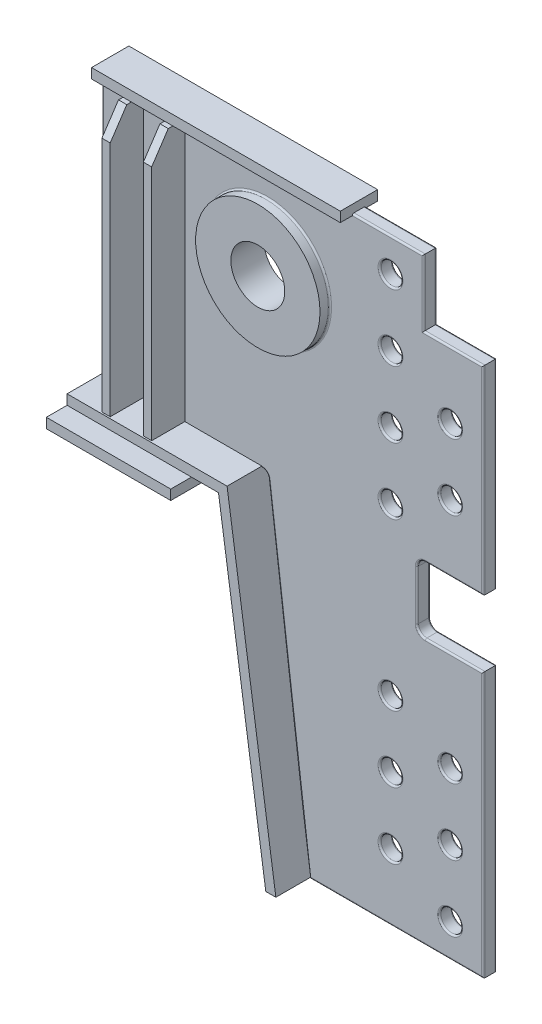
SolidWorks part; units mm, degrees
ref_plane "前视" through (0, 0, 0) normal (0, 0, 1) x (1, 0, 0)
ref_plane "上视" through (0, 0, 0) normal (0, 1, 0) x (1, 0, 0)
ref_plane "右视" through (0, 0, 0) normal (1, 0, 0) x (0, 0, -1)
sketch "草图1" plane through (0, 0, 0) normal (0, 0, 1) x (1, 0, 0)
  line L0 (0, -320) -> (-70, -320)
  line L1 (-72, 0) -> (-460, 0)
  line L2 (-40, 116.6722) -> (-40, -759.2574) construction
  line L3 (0, -720) -> (-210, -720)
  line L4 (-460, 0) -> (-460, -320)
  line L5 (-80, -330) -> (-80, -390)
  line L6 (-70, -400) -> (0, -400)
  line L7 (0, -400) -> (0, -720)
  line L8 (-112, 271.0914) -> (-112, -671.0914) construction
  line L9 (-775.8996, -110) -> (-214.577, -110) construction
  line L15 (-210, -720) -> (-259.124, -327.0077)
  line L16 (-460, -320) -> (-267.0623, -320)
  line L17 (-72, 0) -> (-72, -80)
  line L18 (-72, -80) -> (0, -80)
  line L19 (0, -80) -> (0, -320)
  arc A0 (-80, -330) -> (-70, -320) centre (-70, -330) cw
  arc A1 (-70, -400) -> (-80, -390) centre (-70, -390) cw
  circle A2 centre (-112, -40) radius 13
  circle A3 centre (-112, -120) radius 13
  circle A4 centre (-112, -200) radius 13
  circle A5 centre (-112, -280) radius 13
  circle A6 centre (-40, -160) radius 13
  circle A7 centre (-40, -240) radius 13
  circle A8 centre (-40, -680) radius 13
  circle A9 centre (-40, -600) radius 13
  circle A10 centre (-40, -520) radius 13
  arc A11 (-259.124, -327.0077) -> (-267.0623, -320) centre (-267.0623, -328) ccw
  circle A12 centre (-112, -640) radius 13
  circle A13 centre (-112, -560) radius 13
  circle A14 centre (-112, -480) radius 13
  circle A15 centre (-260, -110) radius 37.5
  point P11 (-80, -320)
  point P49 (-260, -320)
  dimension "D4" = 10
  dimension "D5" = 10
  dimension "D13" = 72
  dimension "D14" = 80
  dimension "D18" = 72
  dimension "D20" = 80
  dimension "D24" = 8
  dimension "D25" = 40
  dimension "D26" = 40
  dimension "D32" = 26
  dimension "D34" = 75
  dimension "D3" = 80
  dimension "D6" = 720
  dimension "D7" = 72
  dimension "D8" = 320
  dimension "D9" = 320
  dimension "D10" = 460
  dimension "D11" = 80
  dimension "D12" = 40
  dimension "D15" = 40
  dimension "D16" = 80
  dimension "D17" = 80
  dimension "D19" = 80
  dimension "D21" = 210
  dimension "D22" = 392.9923
  dimension "D23" = 40
  dimension "D27" = 80
  dimension "D28" = 80
  dimension "D29" = 40
  dimension "D30" = 80
  dimension "D31" = 80
  dimension "D33" = 110
  dimension "D35" = 200
extrude "基体-拉伸" add sketch "草图1" along normal blind 16
sketch "草图2" plane through (0, 0, 16) normal (0, 0, 1) x (1, 0, 0)
  line L0 (-460, 0) -> (-460, -320) construction
  line L1 (-72, 0) -> (-460, 0) construction
  circle A0 centre (-260, -110) radius 32.5
  circle A1 centre (-260, -110) radius 75
  dimension "D1" = 65
  dimension "D4" = 150
  dimension "D2" = 200
  dimension "D3" = 110
extrude "凸台-拉伸1" add sketch "草图2" along normal blind 12 and the other way blind 28
fillet "圆角1" radius 2 28 edges at (-185, -110, 16) (-99, -560, 16) (-27, -600, 16) (-27, -240, 16) (-35, -320, 16) (-77.0711, -322.9289, 16) (-80, -360, 16) (-77.0711, -397.0711, 16) (-35, -400, 16) (0, -560, 16) (-105, -720, 16) (-234.562, -523.5039, 16) (-261.7678, -322.0026, 16) (-363.5311, -320, 16) (-460, -160, 16) (-266, 0, 16) (-27, -680, 16) (-27, -520, 16) (-99, -480, 16) (-99, -640, 16) (-99, -280, 16) (-99, -120, 16) (-72, -40, 16) (-36, -80, 16) (0, -200, 16) (-99, -40, 16) (-99, -200, 16) (-27, -160, 16)
fillet "圆角2" radius 2 28 edges at (-185, -110, 0) (-99, -560, 0) (-27, -600, 0) (-27, -240, 0) (-266, 0, 0) (-460, -160, 0) (-363.5311, -320, 0) (-261.7678, -322.0026, 0) (-234.562, -523.5039, 0) (-105, -720, 0) (0, -560, 0) (-35, -400, 0) (-77.0711, -397.0711, 0) (-80, -360, 0) (-77.0711, -322.9289, 0) (-35, -320, 0) (-27, -680, 0) (-27, -520, 0) (-99, -480, 0) (-99, -640, 0) (-99, -280, 0) (-99, -120, 0) (0, -200, 0) (-36, -80, 0) (-72, -40, 0) (-99, -40, 0) (-99, -200, 0) (-27, -160, 0)
sketch "草图3" plane through (0, 0, 16) normal (0, 0, 1) x (1, 0, 0)
  line L0 (-74, -2) -> (-458, -2) construction
  line L1 (-420, -2) -> (-410, -2)
  line L2 (-420, -2) -> (-420, -318)
  line L3 (-420, -318) -> (-410, -318)
  line L4 (-410, -2) -> (-410, -318)
  line L5 (-458, -318) -> (-267.0623, -318) construction
  line L6 (-460, -320) -> (-460, 0) construction
  line L7 (-370, -2) -> (-360, -2)
  line L8 (-370, -2) -> (-370, -318)
  line L9 (-370, -318) -> (-360, -318)
  line L10 (-360, -2) -> (-360, -318)
  dimension "D1" = 10
  dimension "D2" = 10
  dimension "D3" = 40
  dimension "D4" = 40
extrude "凸台-拉伸2" add sketch "草图3" along normal blind 40 and the other way blind 56
sketch "草图4" plane through (-420, 0, 0) normal (-1, 0, 0) x (0, 0, 1)
  line L0 (-20, -2) -> (-45.5, -32)
  line L1 (0, -2) -> (-40, -2) construction
  line L3 (-20, -2) -> (-45.5, -2)
  line L4 (-45.5, -2) -> (-45.5, -32)
  dimension "D1" = 30
  dimension "D2" = 25.5
extrude "切除-拉伸1" cut sketch "草图4" against normal through all
sketch "草图5" plane through (-420, 0, 0) normal (-1, 0, 0) x (0, 0, 1)
  line L0 (36, -2) -> (56, -32)
  line L1 (56, -2) -> (16, -2) construction
  line L2 (56, -2) -> (56, -318) construction
  line L3 (36, -2) -> (56, -2)
  line L4 (56, -2) -> (56, -32)
  dimension "D1" = 30
extrude "切除-拉伸2" cut sketch "草图5" against normal through all
sketch "草图6" plane through (0, 0, 16) normal (0, 0, 1) x (1, 0, 0)
  line L0 (-460, -320) -> (-460, 0) construction
  line L1 (-267.0623, -318) -> (-460, -318)
  line L2 (-267.0623, -318) -> (-208.2344, -718)
  line L3 (-277.4265, -330) -> (-460, -330)
  line L4 (-460, -318) -> (-460, -330)
  line L6 (-277.4265, -330) -> (-220.3635, -718)
  line L7 (-220.3635, -718) -> (-208.2344, -718)
  dimension "D1" = 12
  dimension "D2" = 12
extrude "凸台-拉伸5" add sketch "草图6" along normal blind 42 and the other way blind 58
sketch "草图7" plane through (0, 0, 0) normal (0, 0, -1) x (-1, 0, 0)
  line L1 (458, -2) -> (158, -2)
  line L2 (458, -2) -> (458, 10)
  line L3 (458, 10) -> (158, 10)
  line L4 (158, -2) -> (158, 10)
  dimension "D1" = 300
  dimension "D2" = 12
extrude "凸台-拉伸6" add sketch "草图7" along normal blind 14.5 and the other way blind 30.5
sketch "草图8" plane through (0, -330, 0) normal (0, -1, 0) x (1, 0, 0)
  line L0 (-515.842, 8) -> (-234.809, 8) construction
  line L1 (-460, -42) -> (-277.4265, -42) construction
  line L2 (-460, 58) -> (-277.4265, 58) construction
  line L4 (-310, 83) -> (-460, 83)
  line L5 (-310, 83) -> (-310, -67)
  line L6 (-310, -67) -> (-460, -67)
  line L7 (-460, 83) -> (-460, -67)
  line L8 (-460, 58) -> (-460, -42) construction
  dimension "D1" = 150
  dimension "D2" = 150
extrude "凸台-拉伸7" add sketch "草图8" along normal blind 12
